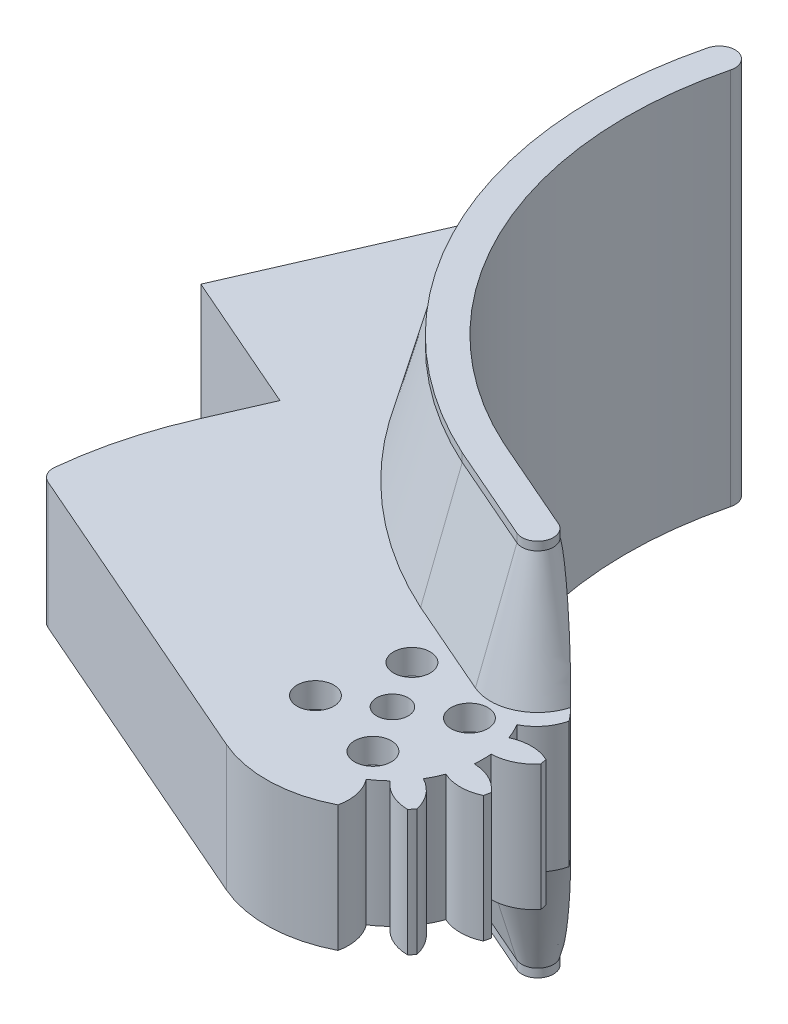
SolidWorks part; units mm, degrees
ref_plane "Plan de face" through (0, 0, 0) normal (0, 0, 1) x (1, 0, 0)
ref_plane "Plan de dessus" through (0, 0, 0) normal (0, 1, 0) x (1, 0, 0)
ref_plane "Plan de droite" through (0, 0, 0) normal (1, 0, 0) x (0, 0, -1)
sketch "Esquisse1" plane through (0, 0, 0) normal (0, 1, 0) x (1, 0, 0)
  line L0 (-21.1447, 0) -> (21.1447, 0) construction
  line L2 (0, 107.7631) -> (107.7631, 0) construction
  line L9 (0, 76.2) -> (0, -76.2) construction
  line L10 (22.4506, 85.3124) -> (49.3914, 112.2532) construction
  line L11 (112.2532, 49.3914) -> (49.3914, 112.2532) construction
  line L12 (85.3124, 22.4506) -> (22.4506, 85.3124) construction
  line L13 (85.3124, 22.4506) -> (112.2532, 49.3914) construction
  line L14 (0, 107.7631) -> (107.7631, 0) construction
  line L15 (0, -76.2) -> (0, -166.9225) construction
  line L16 (12.0681, -77.8609) -> (31.5678, -69.3535) construction
  line L17 (32.3819, -124.4225) -> (154.4572, -71.1636) construction
  line L18 (22.225, -101.1417) -> (-24.6748, 6.3579) construction
  line L19 (37.6806, 33.5622) -> (-24.6748, 6.3579) construction
  line L22 (31.5678, -69.3535) -> (134.1433, -24.602) construction
  line L26 (-73.8821, 18.6512) -> (13.4209, -19.4373) construction
  line L27 (-86.989, -59.0305) -> (-106.4228, -50.5519)
  line L28 (-37.6806, 33.5622) -> (24.6748, 6.3579) construction
  line L29 (-22.225, -101.1417) -> (24.6748, 6.3579) construction
  line L30 (-32.3819, -124.4225) -> (-96.1391, -96.6066)
  line L32 (73.8821, 18.6512) -> (-13.4209, -19.4373) construction
  line L33 (92.0675, -70.6709) -> (86.989, -59.0305) construction
  line L34 (86.989, -59.0305) -> (106.4228, -50.5519) construction
  line L35 (0, 107.7631) -> (-107.7631, 0) construction
  line L36 (-85.3124, 22.4506) -> (-112.2532, 49.3914) construction
  line L37 (-85.3124, 22.4506) -> (-22.4506, 85.3124) construction
  line L38 (-112.2532, 49.3914) -> (-49.3914, 112.2532) construction
  line L39 (-22.4506, 85.3124) -> (-49.3914, 112.2532) construction
  line L40 (0, 107.7631) -> (-107.7631, 0) construction
  line L41 (-92.0675, -70.6709) -> (-86.989, -59.0305)
  line L42 (-12.0681, -77.8609) -> (-31.5678, -69.3535)
  line L43 (22.225, -101.1417) -> (-22.225, -101.1417) construction
  circle A2 centre (22.225, -101.1417) radius 22.225 construction
  arc A3 (154.4572, -71.1636) -> (37.6806, 33.5622) centre (22.225, -101.1417) ccw construction
  circle A4 centre (22.225, -101.1417) radius 25.4 construction
  arc A5 (77.9162, -49.1327) -> (98.23, -95.6944) centre (22.225, -101.1417) cw construction
  arc A6 (112.8374, -33.8973) -> (117.7176, -4.8858) centre (0, 0) ccw construction
  arc A7 (115.5939, -2.8245) -> (117.557, -7.8522) centre (111.2211, -7.429) cw construction
  arc A8 (73.8821, 18.6512) -> (78.273, 22.3194) centre (76.9606, 19.4284) cw construction
  arc A14 (0, -76.2) -> (0, 76.2) centre (0, 0) ccw construction
  arc A17 (112.8374, -33.8973) -> (106.4228, -50.5519) centre (0, 0) cw construction
  arc A18 (-73.8821, 18.6512) -> (-78.273, 22.3194) centre (-76.9606, 19.4284) ccw
  arc A19 (-115.5939, -2.8245) -> (-117.557, -7.8522) centre (-111.2211, -7.429) ccw
  arc A20 (-112.8374, -33.8973) -> (-117.557, -7.8522) centre (0, 0) cw
  arc A21 (-92.0675, -70.6709) -> (-98.0279, -93.3728) centre (-22.225, -101.1417) ccw
  arc A22 (-12.0681, -77.8609) -> (-32.3819, -124.4225) centre (-22.225, -101.1417) cw
  arc A23 (-73.8821, 18.6512) -> (-31.5678, -69.3535) centre (0, 0) ccw
  circle A24 centre (-22.225, -101.1417) radius 22.225 construction
  arc A25 (-115.5939, -2.8245) -> (-78.273, 22.3194) centre (-22.225, -101.1417) cw
  arc A26 (-112.8374, -33.8973) -> (-106.4228, -50.5519) centre (0, 0) ccw
  circle A27 centre (94.8695, -93.6965) radius 3.175 construction
  arc A28 (-96.1391, -96.6066) -> (-98.0279, -93.3728) centre (-94.8695, -93.6965) cw
  dimension "D5" = 3.175
  dimension "D6" = 44.45
  dimension "D8" = 50.8
  dimension "D9" = 76.2
  dimension "D11" = 3.175
  dimension "D12" = 6.35
  dimension "D10" = 38.1
  dimension "D14" = 76.2
  dimension "D17" = 6.35
  dimension "D2" = 38.1
  dimension "D3" = 88.9
  dimension "D4" = 38.1
  dimension "D7" = 95.25
  dimension "D13" = 152.4
  dimension "D15" = 31.75
  dimension "D16" = 12.7
extrude "Boss.-Extru.1" add sketch "Esquisse1" along normal blind 25.4
sketch "Esquisse2" plane through (0, 25.4, 0) normal (0, 1, 0) x (1, 0, 0)
  line L3 (-12.0681, -77.8609) -> (-31.5678, -69.3535) construction
  line L6 (-12.0681, -77.8609) -> (-31.5678, -69.3535)
  line L7 (-14.6073, -83.6811) -> (-34.152, -75.1541)
  arc A3 (-73.8821, 18.6512) -> (-31.5678, -69.3535) centre (0, 0) ccw construction
  arc A9 (-73.8821, 18.6512) -> (-31.5678, -69.3535) centre (0, 0) ccw
  arc A10 (-80.039, 20.2055) -> (-34.152, -75.1541) centre (0, 0) ccw
  arc A11 (-73.8821, 18.6512) -> (-80.039, 20.2055) centre (-76.9606, 19.4284) ccw
  arc A12 (-12.0681, -77.8609) -> (-14.6073, -83.6811) centre (-13.3377, -80.771) cw
  dimension "D1" = 6.35
extrude "Boss.-Extru.3" add sketch "Esquisse2" along normal blind 25.4 and the other way blind 50.8
sketch "Esquisse4" plane through (0, 25.4, 0) normal (0, 1, 0) x (1, 0, 0)
  circle A0 centre (-22.225, -101.1417) radius 3.175
  arc A1 (-32.3819, -124.4225) -> (-12.0681, -77.8609) centre (-22.225, -101.1417) ccw construction
  dimension "D1" = 6.35
extrude "Enlèv. mat.-Extru.2" cut sketch "Esquisse4" against normal blind 4.4
sketch "Esquisse7" plane through (0, 0, 0) normal (0, 1, 0) x (-1, 0, 0)
  arc A115 (-0.3609, 89.5211) -> (6.9511, 91.1441) centre (1.548, 98.2037) ccw
  arc A116 (-0.9424, 90.7287) -> (-0.3609, 89.5211) centre (22.225, 101.1417) ccw
  arc A117 (4.8854, 95.4335) -> (-0.9424, 90.7287) centre (7.0361, 86.8076) ccw
  arc A118 (4.1259, 98.7612) -> (4.8854, 95.4335) centre (22.225, 101.1417) ccw
  arc A119 (-3.1662, 100.4715) -> (4.1259, 98.7612) centre (2.3209, 107.4661) ccw
  arc A120 (-3.1662, 101.8119) -> (-3.1662, 100.4715) centre (22.225, 101.1417) ccw
  arc A121 (4.1259, 103.5222) -> (-3.1662, 101.8119) centre (2.3209, 94.8173) ccw
  arc A122 (4.8854, 106.8499) -> (4.1259, 103.5222) centre (22.225, 101.1417) ccw
  arc A123 (-0.9424, 111.5547) -> (4.8854, 106.8499) centre (7.0361, 115.4758) ccw
  arc A124 (-0.3609, 112.7623) -> (-0.9424, 111.5547) centre (22.225, 101.1417) ccw
  arc A125 (6.9511, 111.1393) -> (-0.3609, 112.7623) centre (1.548, 104.0797) ccw
  arc A126 (9.0793, 113.808) -> (6.9511, 111.1393) centre (22.225, 101.1417) ccw
  arc A127 (5.8699, 120.5754) -> (9.0793, 113.808) centre (14.7596, 120.6465) ccw
  arc A128 (6.9178, 121.4111) -> (5.8699, 120.5754) centre (22.225, 101.1417) ccw
  arc A129 (12.8015, 116.7763) -> (6.9178, 121.4111) centre (4.8704, 112.7601) ccw
  arc A130 (15.8768, 118.2573) -> (12.8015, 116.7763) centre (22.225, 101.1417) ccw
  arc A131 (15.9216, 125.7471) -> (15.8768, 118.2573) centre (23.9617, 121.954) ccw
  arc A132 (17.2283, 126.0454) -> (15.9216, 125.7471) centre (22.225, 101.1417) ccw
  arc A133 (20.5183, 119.3167) -> (17.2283, 126.0454) centre (11.6301, 119.1394) ccw
  arc A134 (23.9317, 119.3167) -> (20.5183, 119.3167) centre (22.225, 101.1417) ccw
  arc A135 (27.2217, 126.0454) -> (23.9317, 119.3167) centre (32.8199, 119.1394) ccw
  arc A136 (28.5284, 125.7471) -> (27.2217, 126.0454) centre (22.225, 101.1417) ccw
  arc A137 (28.5732, 118.2573) -> (28.5284, 125.7471) centre (20.4883, 121.954) ccw
  arc A138 (31.6485, 116.7763) -> (28.5732, 118.2573) centre (22.225, 101.1417) ccw
  arc A139 (37.5322, 121.4111) -> (31.6485, 116.7763) centre (39.5796, 112.7601) ccw
  arc A140 (38.5801, 120.5754) -> (37.5322, 121.4111) centre (22.225, 101.1417) ccw
  arc A141 (35.3707, 113.808) -> (38.5801, 120.5754) centre (29.6904, 120.6465) ccw
  arc A142 (37.4989, 111.1393) -> (35.3707, 113.808) centre (22.225, 101.1417) ccw
  arc A143 (44.8109, 112.7623) -> (37.4989, 111.1393) centre (42.902, 104.0797) ccw
  arc A144 (45.3924, 111.5547) -> (44.8109, 112.7623) centre (22.225, 101.1417) ccw
  arc A145 (39.5646, 106.8499) -> (45.3924, 111.5547) centre (37.4139, 115.4758) ccw
  arc A146 (40.3241, 103.5222) -> (39.5646, 106.8499) centre (22.225, 101.1417) ccw
  arc A147 (47.6162, 101.8119) -> (40.3241, 103.5222) centre (42.1291, 94.8173) ccw
  arc A148 (47.6162, 100.4715) -> (47.6162, 101.8119) centre (22.225, 101.1417) ccw
  arc A149 (40.3241, 98.7612) -> (47.6162, 100.4715) centre (42.1291, 107.4661) ccw
  arc A150 (39.5646, 95.4335) -> (40.3241, 98.7612) centre (22.225, 101.1417) ccw
  arc A151 (45.3924, 90.7287) -> (39.5646, 95.4335) centre (37.4139, 86.8076) ccw
  arc A152 (44.8109, 89.5211) -> (45.3924, 90.7287) centre (22.225, 101.1417) ccw
  arc A153 (37.4989, 91.1441) -> (44.8109, 89.5211) centre (42.902, 98.2037) ccw
  arc A154 (35.3707, 88.4754) -> (37.4989, 91.1441) centre (22.225, 101.1417) ccw
  arc A155 (38.5801, 81.7079) -> (35.3707, 88.4754) centre (29.6904, 81.6369) ccw
  arc A156 (37.5322, 80.8722) -> (38.5801, 81.7079) centre (22.225, 101.1417) ccw
  arc A157 (31.6485, 85.507) -> (37.5322, 80.8722) centre (39.5796, 89.5233) ccw
  arc A158 (28.5732, 84.0261) -> (31.6485, 85.507) centre (22.225, 101.1417) ccw
  arc A159 (28.5284, 76.5363) -> (28.5732, 84.0261) centre (20.4883, 80.3294) ccw
  arc A160 (27.2217, 76.238) -> (28.5284, 76.5363) centre (22.225, 101.1417) ccw
  arc A161 (23.9317, 82.9667) -> (27.2217, 76.238) centre (32.8199, 83.144) ccw
  arc A162 (20.5183, 82.9667) -> (23.9317, 82.9667) centre (22.225, 101.1417) ccw
  arc A163 (17.2283, 76.238) -> (20.5183, 82.9667) centre (11.6301, 83.144) ccw
  arc A164 (15.9216, 76.5363) -> (17.2283, 76.238) centre (22.225, 101.1417) ccw
  arc A165 (15.8768, 84.0261) -> (15.9216, 76.5363) centre (23.9617, 80.3294) ccw
  arc A166 (12.8015, 85.507) -> (15.8768, 84.0261) centre (22.225, 101.1417) ccw
  arc A167 (6.9178, 80.8722) -> (12.8015, 85.507) centre (4.8704, 89.5233) ccw
  arc A168 (5.8699, 81.7079) -> (6.9178, 80.8722) centre (22.225, 101.1417) ccw
  arc A169 (9.0793, 88.4754) -> (5.8699, 81.7079) centre (14.7596, 81.6369) ccw
  arc A170 (6.9511, 91.1441) -> (9.0793, 88.4754) centre (22.225, 101.1417) ccw
sketch "Esquisse11" plane through (0, 0, 0) normal (0, -1, 0) x (1, 0, 0)
  line L1 (10.4046, 138.0046) -> (29.8659, 83.7871)
  line L2 (29.8659, 83.7871) -> (-1.9555, 85.8345)
  line L3 (10.4046, 138.0046) -> (-10.6044, 123.7276)
  arc A0 (-41.6588, 84.7866) -> (-34.8913, 87.996) centre (-41.7298, 93.6763) ccw construction
  arc A1 (-42.4945, 85.8345) -> (-41.6588, 84.7866) centre (-22.225, 101.1417) ccw construction
  arc A2 (-37.8596, 91.7182) -> (-42.4945, 85.8345) centre (-33.8434, 83.7871) ccw construction
  arc A3 (-39.3406, 94.7935) -> (-37.8596, 91.7182) centre (-22.225, 101.1417) ccw construction
  arc A4 (-46.8304, 94.8382) -> (-39.3406, 94.7935) centre (-43.0373, 102.8784) ccw construction
  arc A5 (-47.1287, 96.145) -> (-46.8304, 94.8382) centre (-22.225, 101.1417) ccw construction
  arc A6 (-40.4, 99.435) -> (-47.1287, 96.145) centre (-40.2227, 90.5468) ccw construction
  arc A7 (-40.4, 102.8483) -> (-40.4, 99.435) centre (-22.225, 101.1417) ccw construction
  arc A8 (-47.1287, 106.1384) -> (-40.4, 102.8483) centre (-40.2227, 111.7366) ccw construction
  arc A9 (-46.8304, 107.4451) -> (-47.1287, 106.1384) centre (-22.225, 101.1417) ccw construction
  arc A10 (-39.3406, 107.4899) -> (-46.8304, 107.4451) centre (-43.0373, 99.4049) ccw construction
  arc A11 (-37.8596, 110.5652) -> (-39.3406, 107.4899) centre (-22.225, 101.1417) ccw construction
  arc A12 (-42.4945, 116.4489) -> (-37.8596, 110.5652) centre (-33.8434, 118.4963) ccw construction
  arc A13 (-41.6588, 117.4968) -> (-42.4945, 116.4489) centre (-22.225, 101.1417) ccw construction
  arc A14 (-34.8913, 114.2874) -> (-41.6588, 117.4968) centre (-41.7298, 108.6071) ccw construction
  arc A15 (-32.2226, 116.4156) -> (-34.8913, 114.2874) centre (-22.225, 101.1417) ccw construction
  arc A16 (-33.8456, 123.7276) -> (-32.2226, 116.4156) centre (-25.163, 121.8187) ccw construction
  arc A17 (-32.638, 124.3091) -> (-33.8456, 123.7276) centre (-22.225, 101.1417) ccw construction
  arc A18 (-27.9332, 118.4813) -> (-32.638, 124.3091) centre (-36.5591, 116.3306) ccw construction
  arc A19 (-24.6055, 119.2408) -> (-27.9332, 118.4813) centre (-22.225, 101.1417) ccw construction
  arc A20 (-22.8952, 126.5328) -> (-24.6055, 119.2408) centre (-15.9006, 121.0458) ccw construction
  arc A21 (-21.5548, 126.5328) -> (-22.8952, 126.5328) centre (-22.225, 101.1417) ccw construction
  arc A22 (-19.8445, 119.2408) -> (-21.5548, 126.5328) centre (-28.5494, 121.0458) ccw construction
  arc A23 (-16.5168, 118.4813) -> (-19.8445, 119.2408) centre (-22.225, 101.1417) ccw construction
  arc A24 (-11.812, 124.3091) -> (-16.5168, 118.4813) centre (-7.8909, 116.3306) ccw construction
  arc A25 (-10.6044, 123.7276) -> (-11.812, 124.3091) centre (-22.225, 101.1417) ccw construction
  arc A26 (-12.2274, 116.4156) -> (-10.6044, 123.7276) centre (-19.287, 121.8187) ccw
  arc A27 (-9.5587, 114.2874) -> (-12.2274, 116.4156) centre (-22.225, 101.1417) ccw
  arc A28 (-2.7912, 117.4968) -> (-9.5587, 114.2874) centre (-2.7202, 108.6071) ccw
  arc A29 (-1.9555, 116.4489) -> (-2.7912, 117.4968) centre (-22.225, 101.1417) ccw
  arc A30 (-6.5904, 110.5652) -> (-1.9555, 116.4489) centre (-10.6066, 118.4963) ccw
  arc A31 (-5.1094, 107.4899) -> (-6.5904, 110.5652) centre (-22.225, 101.1417) ccw
  arc A32 (2.3804, 107.4451) -> (-5.1094, 107.4899) centre (-1.4127, 99.4049) ccw
  arc A33 (2.6787, 106.1384) -> (2.3804, 107.4451) centre (-22.225, 101.1417) ccw
  arc A34 (-4.05, 102.8483) -> (2.6787, 106.1384) centre (-4.2273, 111.7366) ccw
  arc A35 (-4.05, 99.435) -> (-4.05, 102.8483) centre (-22.225, 101.1417) ccw
  arc A36 (2.6787, 96.145) -> (-4.05, 99.435) centre (-4.2273, 90.5468) ccw
  arc A37 (2.3804, 94.8382) -> (2.6787, 96.145) centre (-22.225, 101.1417) ccw
  arc A38 (-5.1094, 94.7935) -> (2.3804, 94.8382) centre (-1.4127, 102.8784) ccw
  arc A39 (-6.5904, 91.7182) -> (-5.1094, 94.7935) centre (-22.225, 101.1417) ccw
  arc A40 (-1.9555, 85.8345) -> (-6.5904, 91.7182) centre (-10.6066, 83.7871) ccw
  arc A41 (-2.7912, 84.7866) -> (-1.9555, 85.8345) centre (-22.225, 101.1417) ccw construction
  arc A42 (-9.5587, 87.996) -> (-2.7912, 84.7866) centre (-2.7202, 93.6763) ccw construction
  arc A43 (-12.2274, 85.8678) -> (-9.5587, 87.996) centre (-22.225, 101.1417) ccw construction
  arc A44 (-10.6044, 78.5558) -> (-12.2274, 85.8678) centre (-19.287, 80.4647) ccw construction
  arc A45 (-11.812, 77.9743) -> (-10.6044, 78.5558) centre (-22.225, 101.1417) ccw construction
  arc A46 (-16.5168, 83.8021) -> (-11.812, 77.9743) centre (-7.8909, 85.9528) ccw construction
  arc A47 (-19.8445, 83.0426) -> (-16.5168, 83.8021) centre (-22.225, 101.1417) ccw construction
  arc A48 (-21.5548, 75.7505) -> (-19.8445, 83.0426) centre (-28.5494, 81.2376) ccw construction
  arc A49 (-22.8952, 75.7505) -> (-21.5548, 75.7505) centre (-22.225, 101.1417) ccw construction
  arc A50 (-24.6055, 83.0426) -> (-22.8952, 75.7505) centre (-15.9006, 81.2376) ccw construction
  arc A51 (-27.9332, 83.8021) -> (-24.6055, 83.0426) centre (-22.225, 101.1417) ccw construction
  arc A52 (-32.638, 77.9743) -> (-27.9332, 83.8021) centre (-36.5591, 85.9528) ccw construction
  arc A53 (-33.8456, 78.5558) -> (-32.638, 77.9743) centre (-22.225, 101.1417) ccw construction
  arc A54 (-32.2226, 85.8678) -> (-33.8456, 78.5558) centre (-25.163, 80.4647) ccw construction
  arc A55 (-34.8913, 87.996) -> (-32.2226, 85.8678) centre (-22.225, 101.1417) ccw construction
extrude "Enlèv. mat.-Extru.3" cut sketch "Esquisse11" against normal through all
chamfer "Chanfrein2" distance 6.35 angle 75 4 edges at (-10.4276, 25.4, 82.0406) (-79.3972, 25.4, -21.4639) (-24.3797, 25.4, 79.4176) (-74.3859, 25.4, 35.7944) first distance on face at (-22.225, 25.4, 104.3167)
chamfer "Chanfrein3" distance 6.35 angle 75 4 edges at (-79.3972, 0, -21.4639) (-10.4276, 0, 82.0406) (-74.3859, 0, 35.7944) (-24.3797, 0, 79.4176) first distance on face at (-35.8989, 0, 82.6132)
sketch "Esquisse12" plane through (0, 0, 0) normal (0, -1, 0) x (1, 0, 0)
  circle A0 centre (-22.225, 101.1417) radius 3.175
  dimension "D1" = 6.35
sketch "Esquisse15" plane through (0, 0, 0) normal (0, -1, 0) x (1, 0, 0)
  circle A0 centre (-28.0199, 91.4247) radius 2.2
  circle A1 centre (-12.5081, 95.3468) radius 2.2
  circle A2 centre (-16.4301, 110.8586) radius 2.2
  circle A3 centre (-31.9419, 106.9366) radius 2.2
  dimension "D1" = 4.4
extrude "Enlèv. mat.-Extru.6" cut sketch "Esquisse15" against normal through all
sketch "Esquisse16" plane through (0, 25.4, 0) normal (0, -1, 0) x (1, 0, 0)
  circle A0 centre (-28.0199, 91.4247) radius 3.7
  circle A1 centre (-31.9419, 106.9366) radius 3.7
  circle A2 centre (-16.4301, 110.8586) radius 3.7
  circle A3 centre (-12.5081, 95.3468) radius 3.7
  dimension "D1" = 7.4
extrude "Enlèv. mat.-Extru.7" cut sketch "Esquisse16" along normal blind 5
sketch "Esquisse18" plane through (0, 25.4, 0) normal (0, 1, 0) x (1, 0, 0)
  line L0 (-106.4228, -50.5519) -> (-132.0793, -39.3585)
  line L1 (-132.0793, -39.3585) -> (-103.8842, 25.2678)
  line L2 (-103.8842, 25.2678) -> (-87.0724, 17.9332)
  line L3 (-106.4228, -50.5519) -> (-86.989, -59.0305) construction
  line L4 (-87.0724, 17.9332) -> (-106.4228, -50.5519)
  arc A0 (-115.5939, -2.8245) -> (-117.557, -7.8522) centre (-111.2211, -7.429) ccw construction
extrude "Boss.-Extru.4" add sketch "Esquisse18" against normal blind 25.4
sketch "Esquisse19" plane through (0, 25.4, 0) normal (0, 1, 0) x (1, 0, 0)
  line L0 (-96.1391, -96.6066) -> (-130.503, -81.6144)
  line L1 (-130.503, -81.6144) -> (-87.0724, 17.9332)
  line L2 (-87.0724, 17.9332) -> (-136.8728, 68.8847)
  line L3 (-136.8728, 68.8847) -> (-200.2863, -92.7229)
  line L4 (-200.2863, -92.7229) -> (-96.1391, -96.6066)
  line L5 (-96.1391, -96.6066) -> (-32.3819, -124.4225) construction
extrude "Enlèv. mat.-Extru.8" cut sketch "Esquisse19" against normal through all
extrude "Enlèv. mat.-Extru.9" cut sketch "Esquisse12" against normal through all
